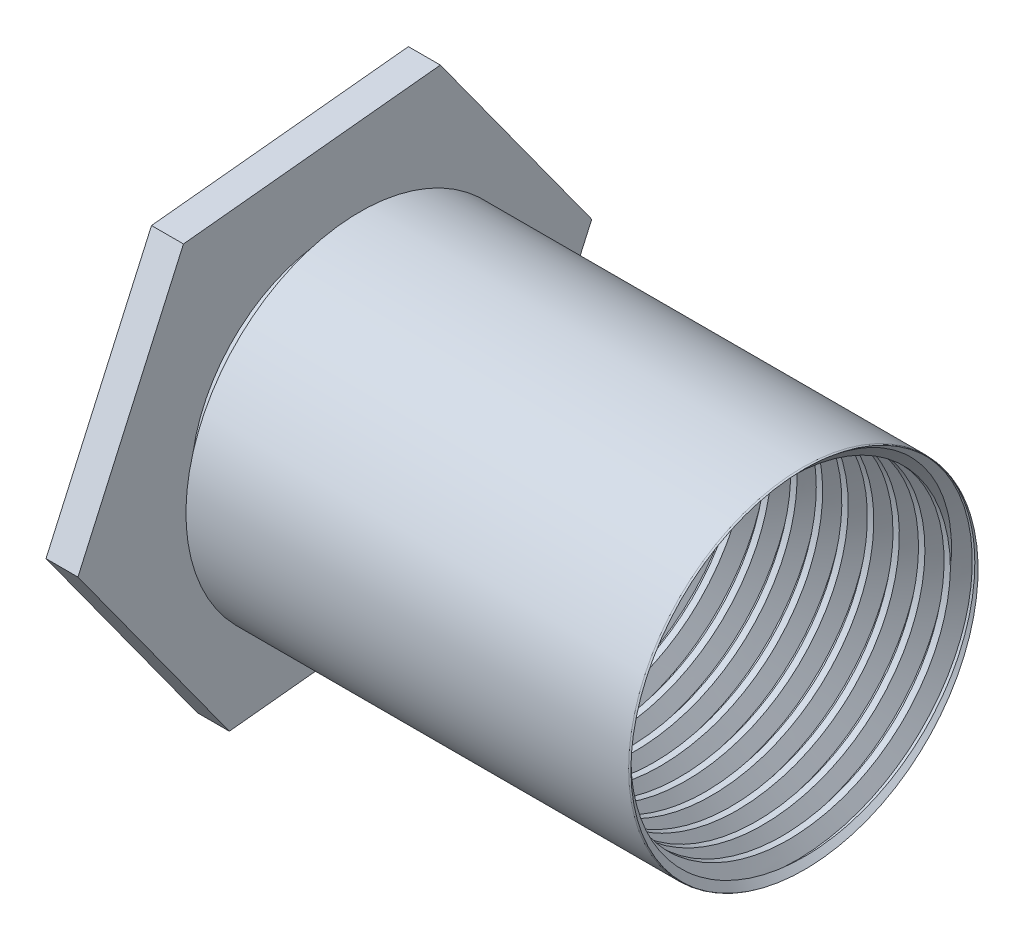
SolidWorks part; units mm, degrees
material "Plain Carbon Steel"
ref_plane "Front Plane" through (0, 0, 0) normal (0, 0, 1) x (1, 0, 0)
ref_plane "Top Plane" through (0, 0, 0) normal (0, 1, 0) x (1, 0, 0)
ref_plane "Right Plane" through (0, 0, 0) normal (1, 0, 0) x (0, 0, -1)
ref_plane "Plane1" through (0.3, 0, 0) normal (1, 0, 0) x (0, 0, -1)
sketch "Sketch1" plane through (0.3, 0, 0) normal (1, 0, 0) x (0, 0, -1)
  line L1 (8.0403, 0.8291) -> (3.3021, 7.3776)
  line L2 (3.3021, 7.3776) -> (-4.7382, 6.5485)
  line L3 (-4.7382, 6.5485) -> (-8.0403, -0.8291)
  line L4 (-8.0403, -0.8291) -> (-3.3021, -7.3776)
  line L5 (-3.3021, -7.3776) -> (4.7382, -6.5485)
  line L6 (4.7382, -6.5485) -> (8.0403, 0.8291)
  circle A0 centre (0, 0) radius 7 construction
  dimension "D1" = 14
extrude "Boss-Extrude1" add sketch "Sketch1" against normal blind 1
ref_plane "Plane2" through (0, 0, 0) normal (0, 0, -1) x (-1, 0, 0)
sketch "Sketch2" plane through (0, 0, 0) normal (0, 0, -1) x (-1, 0, 0)
  line L0 (-15, 5.45) -> (-15, 0)
  line L1 (-15, 0) -> (-0.3, 0)
  line L2 (-0.3, 0) -> (-0.3, 4.5)
  line L3 (-0.3, 4.5) -> (-1.09, 4.5)
  line L4 (-1.09, 4.5) -> (-1.09, 5.45)
  line L5 (-1.09, 5.45) -> (-15, 5.45)
  line L6 (-15, 0) -> (-0.3, 0) construction
  dimension "D1" = 14.7
  dimension "D2" = 0.79
  dimension "D3" = 5.45
  dimension "D4" = 4.5
revolve "Revolve1" add sketch "Sketch2" angle 360 about L6 reverse direction yes
hole_wizard "M8 Clearance Hole1" positions "Sketch4" profile "Sketch3" hole size "M8" standard "ANSI Metric"
sketch "Sketch4" plane through (15, 0, 0) normal (1, 0, 0) x (0, 0, -1)
  point P0 (0, 0)
sketch "Sketch3" plane through (15, 0, 0) normal (0, 1, 0) x (0, 0, -1)
  line L0 (0, 0) -> (0, 16.3868)
  line L1 (0, 16.3868) -> (5, 13.5)
  line L2 (5, 13.5) -> (5, 0)
  line L5 (5, 0) -> (0, 0)
  line L10 (0, 16.3868) -> (-5, 13.5) construction
  line L11 (0, -6.35) -> (0, 107.95) construction
  dimension "Hole Dia." = 10
  dimension "Hole Depth" = 13.5
  dimension "Drill Angle" = 120
chamfer "Chamfer1" distance 0.433 angle 45 1 edges at (15, 0, -5)
fillet "Fillet1" radius 0.1 1 edges at (15, -5.45, 0) tangent propagation no
thread "Thread1" pitch 0.8 method cut profile "Thread Profile1" start angle 0, offset 1, length 13.5, pitch 0.8, diameter 10
ref_plane "Plane3" through (15.567, 0, 5) normal (0, -1, 0) x (0, 0, 1)
sketch "Thread Profile1" plane through (15.567, 0, 5) normal (0, -1, 0) x (0, 0, 1)
  line L0 (0, 0) -> (0, 0.8) construction
  line L1 (0, 0) -> (0.433, 0.25)
  line L2 (0.433, 0.25) -> (0.433, 0.35)
  line L3 (0.433, 0.35) -> (0, 0.6)
  line L4 (0.433, 0.3) -> (0, 0.3) construction
  line L11 (0, 0) -> (0, 0.6)
  point P2 (0, 0)
  dimension "Pitch" = 0.8
  dimension "Profile_Angle" = 60
  dimension "Profile_Land" = 0.1
  dimension "Profile_Height" = 0.433
